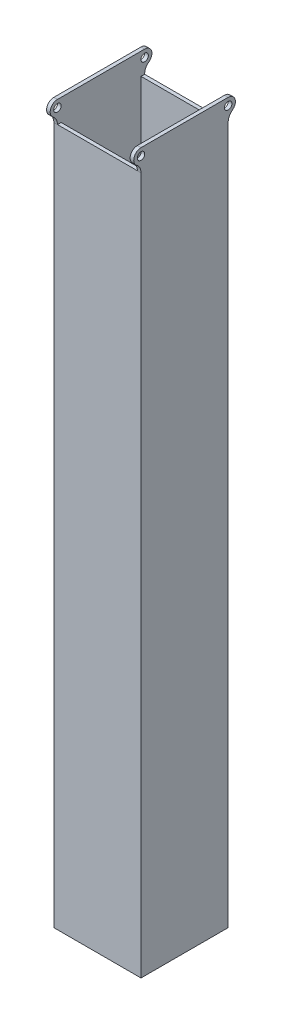
SolidWorks part; units mm, degrees
ref_plane "Front Plane" through (0, 0, 0) normal (0, 0, 1) x (1, 0, 0)
ref_plane "Top Plane" through (0, 0, 0) normal (0, 1, 0) x (1, 0, 0)
ref_plane "Right Plane" through (0, 0, 0) normal (1, 0, 0) x (0, 0, -1)
sketch "Sketch1" plane through (0, 0, 0) normal (0, 1, 0) x (1, 0, 0)
  line L1 (-19.05, -19.05) -> (19.05, -19.05)
  line L2 (-19.05, -19.05) -> (-19.05, 19.05)
  line L3 (-19.05, 19.05) -> (19.05, 19.05)
  line L4 (19.05, -19.05) -> (19.05, 19.05)
  line L5 (-19.05, -19.05) -> (19.05, 19.05) construction
  line L6 (-19.05, 19.05) -> (19.05, -19.05) construction
  point P0 (0, 0)
  dimension "D1" = 38.1
extrude "Extrude-Thin1" add sketch "Sketch1" along normal mid plane 304.8 thin contours L3 L4 L1 L2 thin type one direction reverse wall 1.5875
sketch "Sketch3" plane through (-17.4625, 0, 0) normal (1, 0, 0) x (0, 0, -1)
  line L0 (-19.05, 152.4) -> (19.05, 152.4) construction
  line L1 (-19.05, 152.4) -> (-19.05, -152.4) construction
  line L2 (0, 152.4) -> (0, 161.925) construction
  line L5 (-19.05, 161.925) -> (19.05, 161.925)
  line L6 (19.05, 152.4) -> (-19.05, 152.4)
  circle A5 centre (-19.05, 158.75) radius 3.175
  arc A6 (-19.05, 152.4) -> (-20.955, 156.21) centre (-23.8125, 152.4) ccw
  arc A7 (19.05, 152.4) -> (20.955, 156.21) centre (23.8125, 152.4) cw
  circle A8 centre (19.05, 158.75) radius 3.175
  point P19 (0, 152.4)
  line M2 (-17.4625, -152.4) -> (17.4625, -152.4)
  line M4 (17.4625, 152.4) -> (-17.4625, 152.4)
  dimension "D1" = 6.35
  dimension "D2" = 6.35
extrude "Boss-Extrude1" add sketch "Sketch3" against normal blind 1.5875 contours M2 | L2 L6 A7 A8 L5 M4 | A8 | L6 L2 L5 A5 A6 | A5 region at (-17.4625, 156.9935, 8.8307) region at (-17.4625, 156.9935, -8.8307) region at (-17.4625, 158.75, -19.05)
extrude "Boss-Extrude2" add sketch "Sketch3<3>" against normal blind 1.5875 from surface contours M2 | A8 | L2 L6 A7 A8 L5 M4 | L6 L2 L5 A5 A6 | A5 region at (-17.4625, 156.9935, 8.8307) region at (-17.4625, 156.9935, -8.8307) region at (-17.4625, 158.75, 19.05) region at (-17.4625, 158.75, -19.05) starting at face at (19.05, 0, 0)
sketch "Sketch3<3>" plane through (-17.4625, 0, 0) normal (1, 0, 0) x (0, 0, -1) same geometry as "Sketch3"
hole_wizard "#4 Clearance Hole1" positions "Sketch10" profile "Sketch9" hole size "#4" standard "ANSI Inch" end condition through all
sketch "Sketch10" plane through (-19.05, 0, 0) normal (-1, 0, 0) x (0, 0, 1)
  point P12 (-19.05, 158.75)
  point P15 (19.05, 158.75)
sketch "Sketch9" plane through (-19.05, 158.75, -19.05) normal (0, 1, 0) x (0, 0, 1)
  line L0 (0, 0) -> (0, 38.1)
  line L1 (0, 38.1) -> (1.6319, 38.1)
  line L2 (1.6319, 38.1) -> (1.632, 0)
  line L5 (1.632, 0) -> (0, 0)
  line L11 (0, -6.35) -> (0, 107.95) construction
  dimension "Thru Hole Dia." = 3.2639
  dimension "Thru Hole Depth" = 38.1
